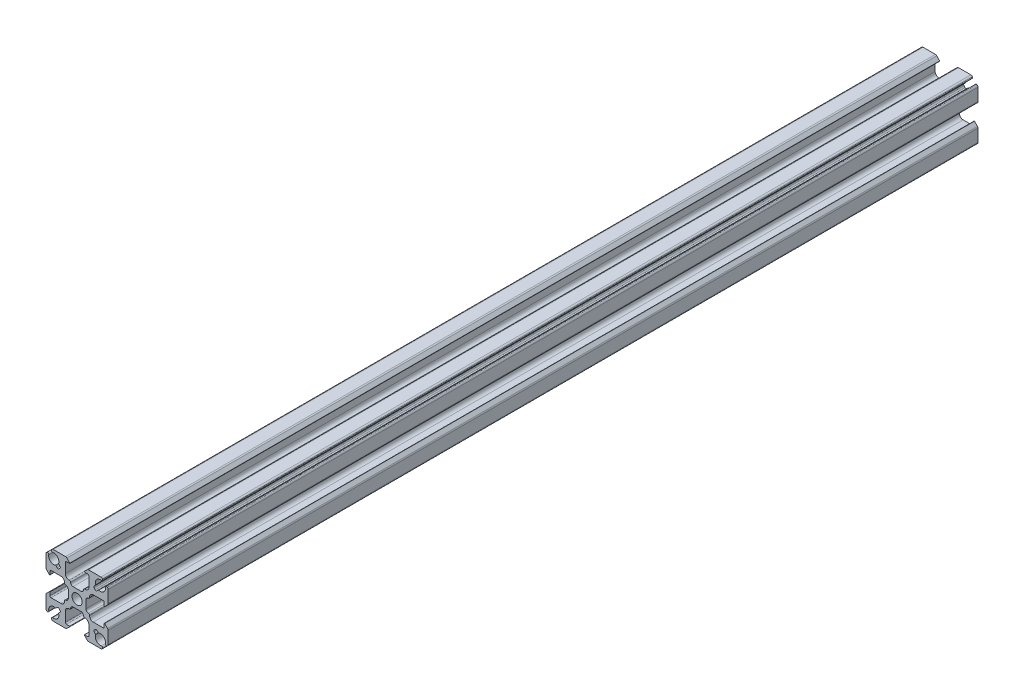
SolidWorks part; units mm, degrees
ref_plane "Front Plane" through (0, 0, 0) normal (0, 0, 1) x (1, 0, 0)
ref_plane "Top Plane" through (0, 0, 0) normal (0, 1, 0) x (1, 0, 0)
ref_plane "Right Plane" through (0, 0, 0) normal (1, 0, 0) x (0, 0, -1)
ref_plane "Plane1" through (0, 0, 0) normal (0, 0, -1) x (-1, 0, 0)
sketch "Sketch1" plane through (0, 0, 0) normal (0, 0, -1) x (-1, 0, 0)
  line L0 (-7.4885, 8.6199) -> (-6.9856, 8.117)
  line L1 (-6.9856, 7.4099) -> (-7.4099, 6.9856)
  line L2 (-8.117, 6.9856) -> (-8.6199, 7.4885)
  line L3 (-12.7, 9.7594) -> (-12.7, 4.7107)
  line L4 (-12.4803, 4.1803) -> (-11.2707, 2.9707)
  line L5 (-11.1, 3.0414) -> (-11.1, 4.325)
  line L6 (-10.6, 4.825) -> (-6.6, 4.825)
  line L7 (-5.1, 3.325) -> (-5.1, 3.15)
  line L8 (-3.6, 1.65) -> (-3.6, -1.65)
  line L9 (-5.1, -3.15) -> (-5.1, -3.325)
  line L10 (-6.6, -4.825) -> (-10.6, -4.825)
  line L11 (-11.1, -4.325) -> (-11.1, -3.0414)
  line L12 (-11.2707, -2.9707) -> (-12.4803, -4.1803)
  line L13 (-12.7, -4.7107) -> (-12.7, -9.7594)
  line L14 (-8.6199, -7.4885) -> (-8.117, -6.9856)
  line L15 (-7.4099, -6.9856) -> (-6.9856, -7.4099)
  line L16 (-6.9856, -8.117) -> (-7.4885, -8.6199)
  line L17 (-9.7594, -12.7) -> (-4.7107, -12.7)
  line L18 (-4.1803, -12.4803) -> (-2.9707, -11.2707)
  line L19 (-3.0414, -11.1) -> (-4.325, -11.1)
  line L20 (-4.825, -10.6) -> (-4.825, -6.6)
  line L21 (-3.325, -5.1) -> (-3.15, -5.1)
  line L22 (-1.65, -3.6) -> (1.65, -3.6)
  line L23 (3.15, -5.1) -> (3.325, -5.1)
  line L24 (4.825, -6.6) -> (4.825, -10.6)
  line L25 (4.325, -11.1) -> (3.0414, -11.1)
  line L26 (2.9707, -11.2707) -> (4.1803, -12.4803)
  line L27 (4.7107, -12.7) -> (9.7594, -12.7)
  line L28 (7.4885, -8.6199) -> (6.9856, -8.117)
  line L29 (6.9856, -7.4099) -> (7.4099, -6.9856)
  line L30 (8.117, -6.9856) -> (8.6199, -7.4885)
  line L31 (12.7, -9.7594) -> (12.7, -4.7107)
  line L32 (12.4803, -4.1803) -> (11.2707, -2.9707)
  line L33 (11.1, -3.0414) -> (11.1, -4.325)
  line L34 (10.6, -4.825) -> (6.6, -4.825)
  line L35 (5.1, -3.325) -> (5.1, -3.15)
  line L36 (3.6, -1.65) -> (3.6, 1.65)
  line L37 (5.1, 3.15) -> (5.1, 3.325)
  line L38 (6.6, 4.825) -> (10.6, 4.825)
  line L39 (11.1, 4.325) -> (11.1, 3.0414)
  line L40 (11.2707, 2.9707) -> (12.4803, 4.1803)
  line L41 (12.7, 4.7107) -> (12.7, 9.7594)
  line L42 (8.6199, 7.4885) -> (8.117, 6.9856)
  line L43 (7.4099, 6.9856) -> (6.9856, 7.4099)
  line L44 (6.9856, 8.117) -> (7.4885, 8.6199)
  line L45 (9.7594, 12.7) -> (4.7107, 12.7)
  line L46 (4.1803, 12.4803) -> (2.9707, 11.2707)
  line L47 (3.0414, 11.1) -> (4.325, 11.1)
  line L48 (4.825, 10.6) -> (4.825, 6.6)
  line L49 (3.325, 5.1) -> (3.15, 5.1)
  line L50 (1.65, 3.6) -> (-1.65, 3.6)
  line L51 (-3.15, 5.1) -> (-3.325, 5.1)
  line L52 (-4.825, 6.6) -> (-4.825, 10.6)
  line L53 (-4.325, 11.1) -> (-3.0414, 11.1)
  line L54 (-2.9707, 11.2707) -> (-4.1803, 12.4803)
  line L55 (-4.7107, 12.7) -> (-9.7594, 12.7)
  circle A0 centre (0, 0) radius 2.08
  arc A1 (-9.7594, 12.7) -> (-10.4266, 12.2927) centre (-9.7594, 11.95) ccw
  arc A2 (-10.4266, 12.2927) -> (-9.8933, 11.5721) centre (-9.9818, 12.0642) ccw
  arc A3 (-9.8933, 11.5721) -> (-7.5492, 8.8748) centre (-9.525, 9.525) cw
  arc A4 (-7.5492, 8.8748) -> (-7.4885, 8.6199) centre (-7.3118, 8.7967) ccw
  arc A5 (-6.9856, 8.117) -> (-6.9856, 7.4099) centre (-7.3392, 7.7635) cw
  arc A6 (-7.4099, 6.9856) -> (-8.117, 6.9856) centre (-7.7635, 7.3392) cw
  arc A7 (-8.6199, 7.4885) -> (-8.8748, 7.5492) centre (-8.7967, 7.3118) ccw
  arc A8 (-8.8748, 7.5492) -> (-11.5721, 9.8933) centre (-9.525, 9.525) cw
  arc A9 (-11.5721, 9.8933) -> (-12.2927, 10.4266) centre (-12.0642, 9.9818) ccw
  arc A10 (-12.2927, 10.4266) -> (-12.7, 9.7594) centre (-11.95, 9.7594) ccw
  arc A11 (-12.7, 4.7107) -> (-12.4803, 4.1803) centre (-11.95, 4.7107) ccw
  arc A12 (-11.2707, 2.9707) -> (-11.1, 3.0414) centre (-11.2, 3.0414) ccw
  arc A13 (-11.1, 4.325) -> (-10.6, 4.825) centre (-10.6, 4.325) cw
  arc A14 (-6.6, 4.825) -> (-5.1, 3.325) centre (-6.6, 3.325) cw
  arc A15 (-5.1, 3.15) -> (-4.6, 2.65) centre (-4.6, 3.15) ccw
  arc A16 (-4.6, 2.65) -> (-3.6, 1.65) centre (-4.6, 1.65) cw
  arc A17 (-3.6, -1.65) -> (-4.6, -2.65) centre (-4.6, -1.65) cw
  arc A18 (-4.6, -2.65) -> (-5.1, -3.15) centre (-4.6, -3.15) ccw
  arc A19 (-5.1, -3.325) -> (-6.6, -4.825) centre (-6.6, -3.325) cw
  arc A20 (-10.6, -4.825) -> (-11.1, -4.325) centre (-10.6, -4.325) cw
  arc A21 (-11.1, -3.0414) -> (-11.2707, -2.9707) centre (-11.2, -3.0414) ccw
  arc A22 (-12.4803, -4.1803) -> (-12.7, -4.7107) centre (-11.95, -4.7107) ccw
  arc A23 (-12.7, -9.7594) -> (-12.2927, -10.4266) centre (-11.95, -9.7594) ccw
  arc A24 (-12.2927, -10.4266) -> (-11.5721, -9.8933) centre (-12.0642, -9.9818) ccw
  arc A25 (-11.5721, -9.8933) -> (-8.8748, -7.5492) centre (-9.525, -9.525) cw
  arc A26 (-8.8748, -7.5492) -> (-8.6199, -7.4885) centre (-8.7967, -7.3118) ccw
  arc A27 (-8.117, -6.9856) -> (-7.4099, -6.9856) centre (-7.7635, -7.3392) cw
  arc A28 (-6.9856, -7.4099) -> (-6.9856, -8.117) centre (-7.3392, -7.7635) cw
  arc A29 (-7.4885, -8.6199) -> (-7.5492, -8.8748) centre (-7.3118, -8.7967) ccw
  arc A30 (-7.5492, -8.8748) -> (-9.8933, -11.5721) centre (-9.525, -9.525) cw
  arc A31 (-9.8933, -11.5721) -> (-10.4266, -12.2927) centre (-9.9818, -12.0642) ccw
  arc A32 (-10.4266, -12.2927) -> (-9.7594, -12.7) centre (-9.7594, -11.95) ccw
  arc A33 (-4.7107, -12.7) -> (-4.1803, -12.4803) centre (-4.7107, -11.95) ccw
  arc A34 (-2.9707, -11.2707) -> (-3.0414, -11.1) centre (-3.0414, -11.2) ccw
  arc A35 (-4.325, -11.1) -> (-4.825, -10.6) centre (-4.325, -10.6) cw
  arc A36 (-4.825, -6.6) -> (-3.325, -5.1) centre (-3.325, -6.6) cw
  arc A37 (-3.15, -5.1) -> (-2.65, -4.6) centre (-3.15, -4.6) ccw
  arc A38 (-2.65, -4.6) -> (-1.65, -3.6) centre (-1.65, -4.6) cw
  arc A39 (1.65, -3.6) -> (2.65, -4.6) centre (1.65, -4.6) cw
  arc A40 (2.65, -4.6) -> (3.15, -5.1) centre (3.15, -4.6) ccw
  arc A41 (3.325, -5.1) -> (4.825, -6.6) centre (3.325, -6.6) cw
  arc A42 (4.825, -10.6) -> (4.325, -11.1) centre (4.325, -10.6) cw
  arc A43 (3.0414, -11.1) -> (2.9707, -11.2707) centre (3.0414, -11.2) ccw
  arc A44 (4.1803, -12.4803) -> (4.7107, -12.7) centre (4.7107, -11.95) ccw
  arc A45 (9.7594, -12.7) -> (10.4266, -12.2927) centre (9.7594, -11.95) ccw
  arc A46 (10.4266, -12.2927) -> (9.8933, -11.5721) centre (9.9818, -12.0642) ccw
  arc A47 (9.8933, -11.5721) -> (7.5492, -8.8748) centre (9.525, -9.525) cw
  arc A48 (7.5492, -8.8748) -> (7.4885, -8.6199) centre (7.3118, -8.7967) ccw
  arc A49 (6.9856, -8.117) -> (6.9856, -7.4099) centre (7.3392, -7.7635) cw
  arc A50 (7.4099, -6.9856) -> (8.117, -6.9856) centre (7.7635, -7.3392) cw
  arc A51 (8.6199, -7.4885) -> (8.8748, -7.5492) centre (8.7967, -7.3118) ccw
  arc A52 (8.8748, -7.5492) -> (11.5721, -9.8933) centre (9.525, -9.525) cw
  arc A53 (11.5721, -9.8933) -> (12.2927, -10.4266) centre (12.0642, -9.9818) ccw
  arc A54 (12.2927, -10.4266) -> (12.7, -9.7594) centre (11.95, -9.7594) ccw
  arc A55 (12.7, -4.7107) -> (12.4803, -4.1803) centre (11.95, -4.7107) ccw
  arc A56 (11.2707, -2.9707) -> (11.1, -3.0414) centre (11.2, -3.0414) ccw
  arc A57 (11.1, -4.325) -> (10.6, -4.825) centre (10.6, -4.325) cw
  arc A58 (6.6, -4.825) -> (5.1, -3.325) centre (6.6, -3.325) cw
  arc A59 (5.1, -3.15) -> (4.6, -2.65) centre (4.6, -3.15) ccw
  arc A60 (4.6, -2.65) -> (3.6, -1.65) centre (4.6, -1.65) cw
  arc A61 (3.6, 1.65) -> (4.6, 2.65) centre (4.6, 1.65) cw
  arc A62 (4.6, 2.65) -> (5.1, 3.15) centre (4.6, 3.15) ccw
  arc A63 (5.1, 3.325) -> (6.6, 4.825) centre (6.6, 3.325) cw
  arc A64 (10.6, 4.825) -> (11.1, 4.325) centre (10.6, 4.325) cw
  arc A65 (11.1, 3.0414) -> (11.2707, 2.9707) centre (11.2, 3.0414) ccw
  arc A66 (12.4803, 4.1803) -> (12.7, 4.7107) centre (11.95, 4.7107) ccw
  arc A67 (12.7, 9.7594) -> (12.2927, 10.4266) centre (11.95, 9.7594) ccw
  arc A68 (12.2927, 10.4266) -> (11.5721, 9.8933) centre (12.0642, 9.9818) ccw
  arc A69 (11.5721, 9.8933) -> (8.8748, 7.5492) centre (9.525, 9.525) cw
  arc A70 (8.8748, 7.5492) -> (8.6199, 7.4885) centre (8.7967, 7.3118) ccw
  arc A71 (8.117, 6.9856) -> (7.4099, 6.9856) centre (7.7635, 7.3392) cw
  arc A72 (6.9856, 7.4099) -> (6.9856, 8.117) centre (7.3392, 7.7635) cw
  arc A73 (7.4885, 8.6199) -> (7.5492, 8.8748) centre (7.3118, 8.7967) ccw
  arc A74 (7.5492, 8.8748) -> (9.8933, 11.5721) centre (9.525, 9.525) cw
  arc A75 (9.8933, 11.5721) -> (10.4266, 12.2927) centre (9.9818, 12.0642) ccw
  arc A76 (10.4266, 12.2927) -> (9.7594, 12.7) centre (9.7594, 11.95) ccw
  arc A77 (4.7107, 12.7) -> (4.1803, 12.4803) centre (4.7107, 11.95) ccw
  arc A78 (2.9707, 11.2707) -> (3.0414, 11.1) centre (3.0414, 11.2) ccw
  arc A79 (4.325, 11.1) -> (4.825, 10.6) centre (4.325, 10.6) cw
  arc A80 (4.825, 6.6) -> (3.325, 5.1) centre (3.325, 6.6) cw
  arc A81 (3.15, 5.1) -> (2.65, 4.6) centre (3.15, 4.6) ccw
  arc A82 (2.65, 4.6) -> (1.65, 3.6) centre (1.65, 4.6) cw
  arc A83 (-1.65, 3.6) -> (-2.65, 4.6) centre (-1.65, 4.6) cw
  arc A84 (-2.65, 4.6) -> (-3.15, 5.1) centre (-3.15, 4.6) ccw
  arc A85 (-3.325, 5.1) -> (-4.825, 6.6) centre (-3.325, 6.6) cw
  arc A86 (-4.825, 10.6) -> (-4.325, 11.1) centre (-4.325, 10.6) cw
  arc A87 (-3.0414, 11.1) -> (-2.9707, 11.2707) centre (-3.0414, 11.2) ccw
  arc A88 (-4.1803, 12.4803) -> (-4.7107, 12.7) centre (-4.7107, 11.95) ccw
extrude "Boss-Extrude1" add sketch "Sketch1" against normal mid plane 355.6
hole_wizard "Ø6.4 (6.4) Diameter Hole1" positions "Sketch3" profile "Sketch2" hole size "Ø6.4" standard "ANSI Metric" end condition through all
sketch "Sketch3" plane through (3.6, 0, 0) normal (1, 0, 0) x (0, 0, -1)
  point P0 (-137.8, 0)
  point P3 (-17.8, 0)
  point P6 (102.2, 0)
sketch "Sketch2" plane through (3.6, 0, 137.8) normal (0, 1, 0) x (0, 0, -1)
  line L0 (0, 0) -> (0, 16.3)
  line L1 (0, 16.3) -> (3.2, 16.3)
  line L2 (3.2, 16.3) -> (3.2, 0)
  line L5 (3.2, 0) -> (0, 0)
  line L11 (0, -6.35) -> (0, 107.95) construction
  dimension "Thru Hole Dia." = 6.4
  dimension "Thru Hole Depth" = 16.3
